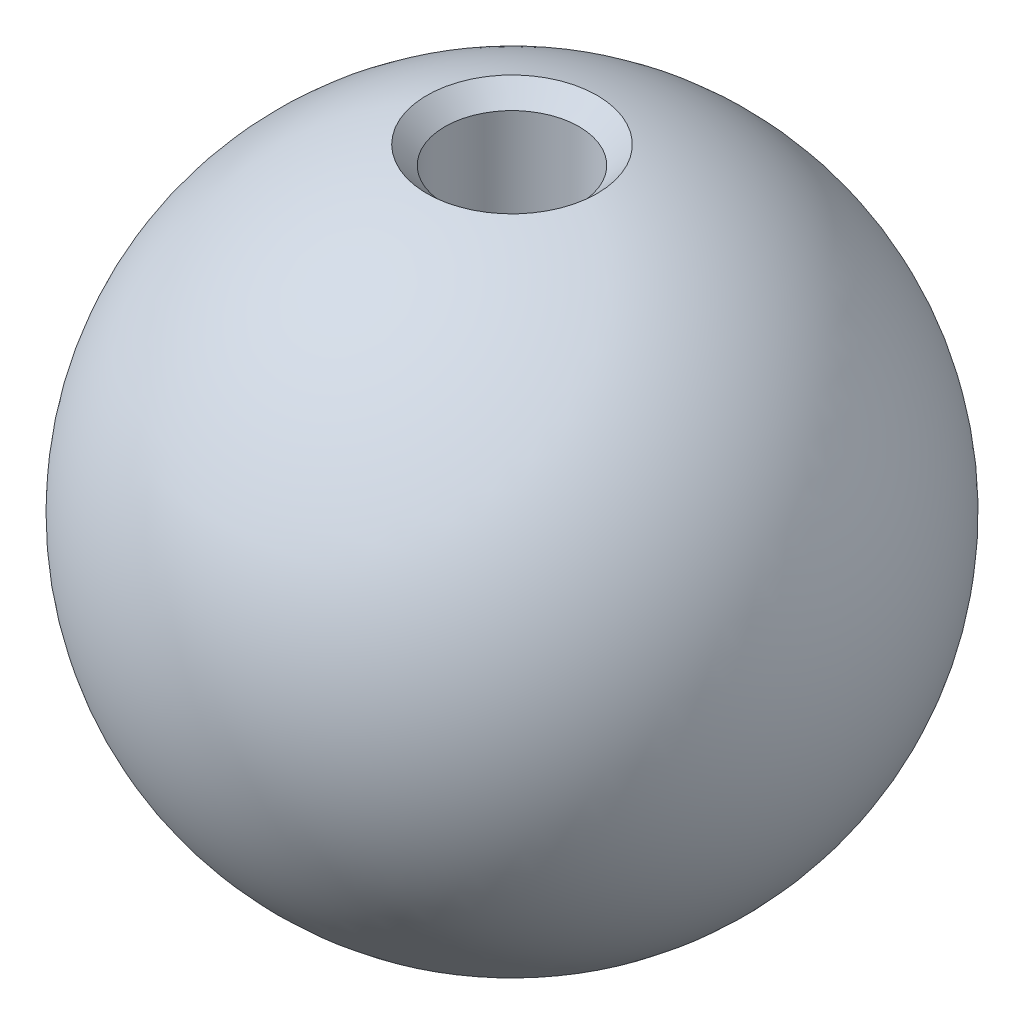
SolidWorks part; units mm, degrees
ref_plane "Ön Düzlem" through (0, 0, 0) normal (0, 0, 1) x (1, 0, 0)
ref_plane "Üst Düzlem" through (0, 0, 0) normal (0, 1, 0) x (1, 0, 0)
ref_plane "Sağ Düzlem" through (0, 0, 0) normal (1, 0, 0) x (0, 0, -1)
sketch "Çizim1" plane through (0, 0, 0) normal (0, 0, 1) x (1, 0, 0)
  line L0 (0, 19.5212) -> (0, -20.1612) construction
  circle A0 centre (0, 0) radius 14.75
  dimension "D1" = 29.5
revolve "Döndür2" add sketch "Çizim1" angle 360 about L0 region at (6.2601, 0, 0)
ref_plane "Düzlem1" through (0, 14.75, 0) normal (0, 1, 0) x (1, 0, 0)
sketch "Çizim2" plane through (0, 14.75, 0) normal (0, 1, 0) x (1, 0, 0)
  circle A0 centre (0, 0) radius 3
  dimension "D1" = 6
extrude "Kes-Ekstrüzyon1" cut sketch "Çizim2" against normal blind 20
chamfer "Pah1" distance 1 angle 45 1 edges at (0, 14.4417, -3) first distance on face at (0, -5.25, 3)
chamfer "Pah2" distance 1 angle 45 1 edges at (0, -5.25, 3)
